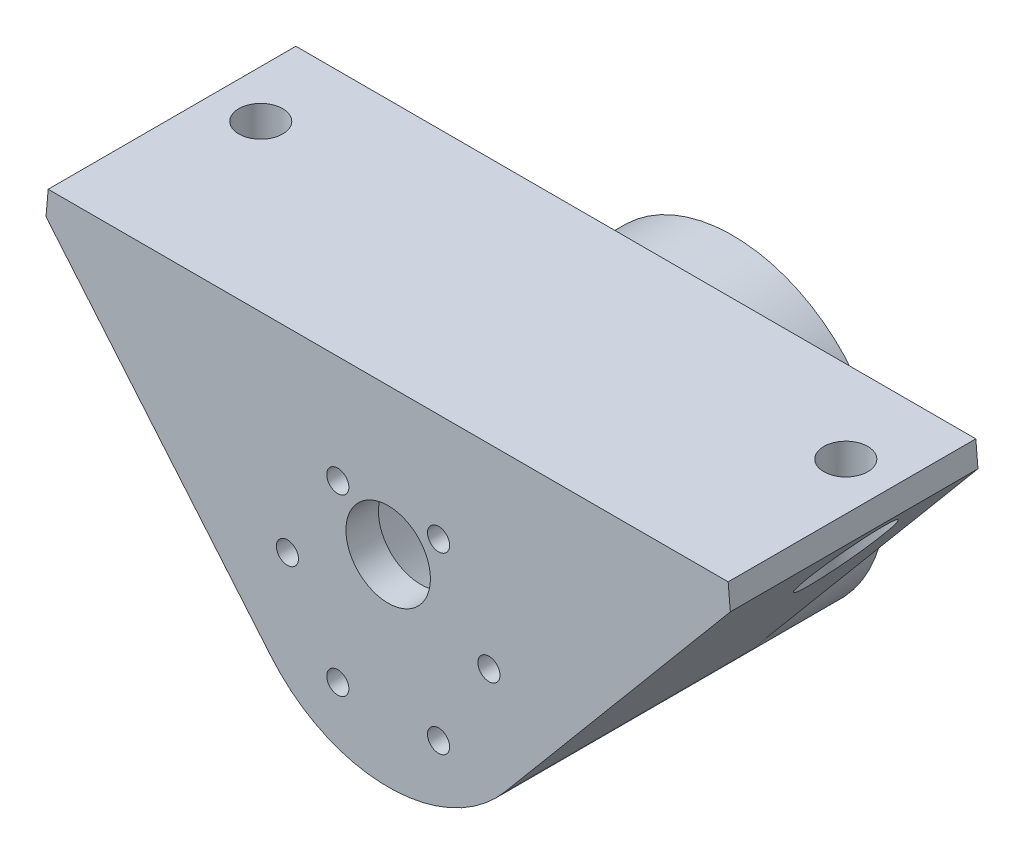
SolidWorks part; units mm, degrees
ref_plane "Front Plane" through (0, 0, 0) normal (0, 0, 1) x (1, 0, 0)
ref_plane "Top Plane" through (0, 0, 0) normal (0, 1, 0) x (1, 0, 0)
ref_plane "Right Plane" through (0, 0, 0) normal (1, 0, 0) x (0, 0, -1)
sketch "Sketch1" plane through (0, 0, 0) normal (0, 0, 1) x (1, 0, 0)
  circle A0 centre (0, 0) radius 15.5
  circle A1 centre (0, 0) radius 18.5
  circle A2 centre (0, 7.5) radius 6.5
  circle A3 centre (0, 0) radius 23.5
  dimension "D1" = 31
  dimension "D2" = 37
  dimension "D3" = 13
  dimension "D4" = 7.5
  dimension "D5" = 5
extrude "Boss-Extrude1" add sketch "Sketch1" against normal blind 48 contours A3 A1 region at (-22.8353, 0, 0)
extrude "Boss-Extrude2" add sketch "Sketch1<3>" along normal blind 5 contours A3 A1 | A1 A0 | A0 A2 region at (0, -1.6004, 0) region at (-17.9767, 0, 0) region at (-22.8353, 0, 0)
sketch "Sketch1<3>" plane through (0, 0, 0) normal (0, 0, 1) x (1, 0, 0) same geometry as "Sketch1"
sketch "Sketch2" plane through (0, 0, 5) normal (0, 0, 1) x (1, 0, 0)
  line L0 (0, 0) -> (-15.5, 0) construction
  circle A0 centre (0, 0) radius 15.5 construction
  circle A1 centre (0, 0) radius 15.5 construction
  point P4 (-15.5, 0)
hole_wizard "M3 Clearance Hole1" positions "Sketch2" profile "Sketch3" hole size "M3" standard "ANSI Metric" end condition through all
sketch "Sketch3" plane through (-15.5, 0, 5) normal (1, 0, 0) x (0, -1, 0)
  line L0 (0, 0) -> (0, 53)
  line L1 (0, 53) -> (1.7, 53)
  line L2 (1.7, 53) -> (1.7, 0)
  line L5 (1.7, 0) -> (0, 0)
  line L11 (0, -6.35) -> (0, 107.95) construction
  dimension "Thru Hole Dia." = 3.4
  dimension "Thru Hole Depth" = 53
pattern_circular "CirPattern1" count 6 over 360 about axis through (0, 0, -48) along (0, 0, 1) of "M3 Clearance Hole1" reverse direction yes
sketch "Sketch5" plane through (0, 0, 5) normal (0, 0, 1) x (1, 0, 0)
  line L0 (-55.8501, 30) -> (55.8501, 30)
  line L1 (-55.8501, 30) -> (-18.002, -15.1055)
  line L2 (55.8501, 30) -> (18.002, -15.1055)
  circle A0 centre (0, 0) radius 23.5 construction
  circle A1 centre (0, 0) radius 23.5
  circle M11 centre (0, 0) radius 23.5
  dimension "D1" = 30
  dimension "D2" = 50
extrude "Boss-Extrude3" add sketch "Sketch5" against normal blind 38.1 contours L2 L0 L1 M11 region at (0, 28.7954, 5)
sketch "Sketch6" plane through (0, 30, 0) normal (0, 1, 0) x (1, 0, 0)
  line L0 (-45, 20.4) -> (45, 20.4) construction
  line L2 (-55.8501, -5) -> (55.8501, -5) construction
  point P3 (0, 20.4)
  dimension "D1" = 90
  dimension "D2" = 25.4
hole_wizard "1/4 Clearance Hole1" positions "Sketch7" profile "Sketch8" hole size "1/4" standard "ANSI Inch" end condition through all
sketch "Sketch7" plane through (0, 30, 0) normal (0, 1, 0) x (1, 0, 0)
  point P0 (-45, 20.4)
  point P3 (45, 20.4)
sketch "Sketch8" plane through (-45, 30, -20.4) normal (1, 0, 0) x (0, 0, 1)
  line L0 (0, 0) -> (0, 53.5)
  line L1 (0, 53.5) -> (3.3782, 53.5)
  line L2 (3.3782, 53.5) -> (3.3782, 0)
  line L5 (3.3782, 0) -> (0, 0)
  line L11 (0, -6.35) -> (0, 107.95) construction
  dimension "Thru Hole Dia." = 6.7564
  dimension "Thru Hole Depth" = 53.5
ref_plane "Plane2" through (0, 25, 0) normal (0, 1, 0) x (1, 0, 0)
sketch "Sketch9" plane through (0, 25, 0) normal (0, 1, 0) x (1, 0, 0)
  circle A0 centre (-45, 20.4) radius 5.715
  circle A1 centre (45, 20.4) radius 5.715
  dimension "D1" = 11.43
extrude "Cut-Extrude1" cut sketch "Sketch9" against normal through all
chamfer "Chamfer1" distance 5 angle 45 2 edges at (55.8501, 30, -14.05) (-55.8501, 30, -14.05) first distance on face at (50.715, 23.8803, -20.4) first distance on face at (-50.715, 23.8803, -20.4)
